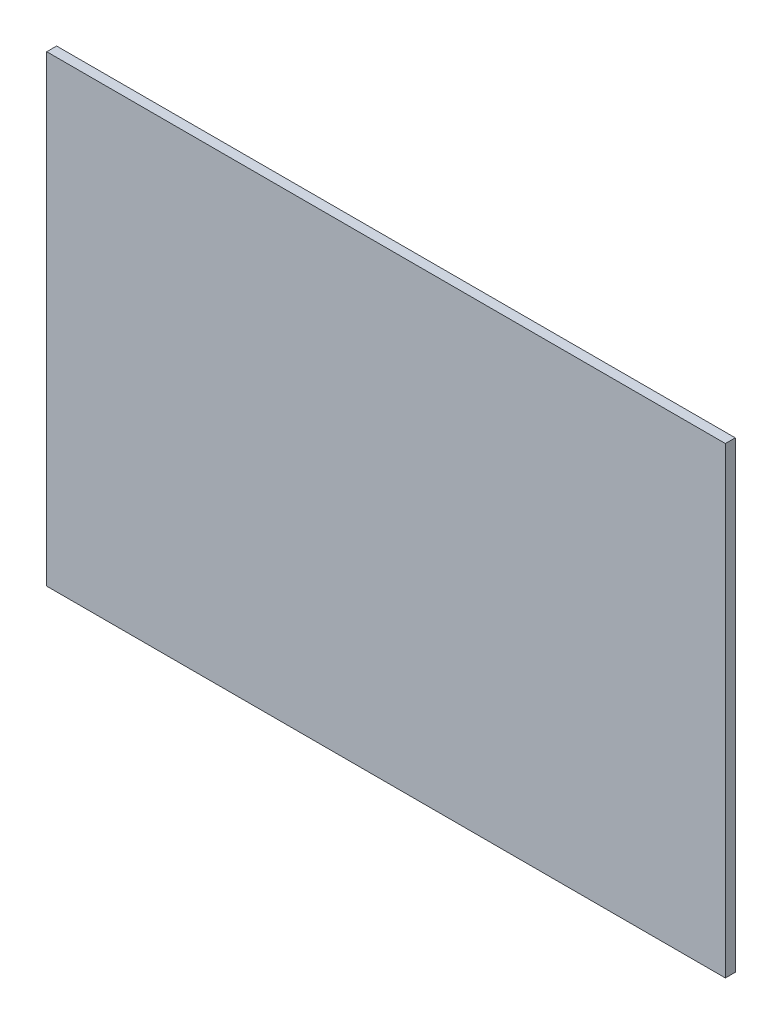
SolidWorks part; units mm, degrees
material "PET"
ref_plane "Front Plane" through (0, 0, 0) normal (0, 0, 1) x (1, 0, 0)
ref_plane "Top Plane" through (0, 0, 0) normal (0, 1, 0) x (1, 0, 0)
ref_plane "Right Plane" through (0, 0, 0) normal (1, 0, 0) x (0, 0, -1)
sketch "Sketch1" plane through (0, 0, 0) normal (0, 0, 1) x (1, 0, 0)
  line L1 (-28.5714, 258.1048) -> (383.4286, 258.1048)
  line L2 (-28.5714, 258.1048) -> (-28.5714, -22.8952)
  line L3 (-28.5714, -22.8952) -> (383.4286, -22.8952)
  line L4 (383.4286, 258.1048) -> (383.4286, -22.8952)
  dimension "D1" = 281
  dimension "D2" = 412
extrude "Boss-Extrude1" add sketch "Sketch1" along normal blind 6
